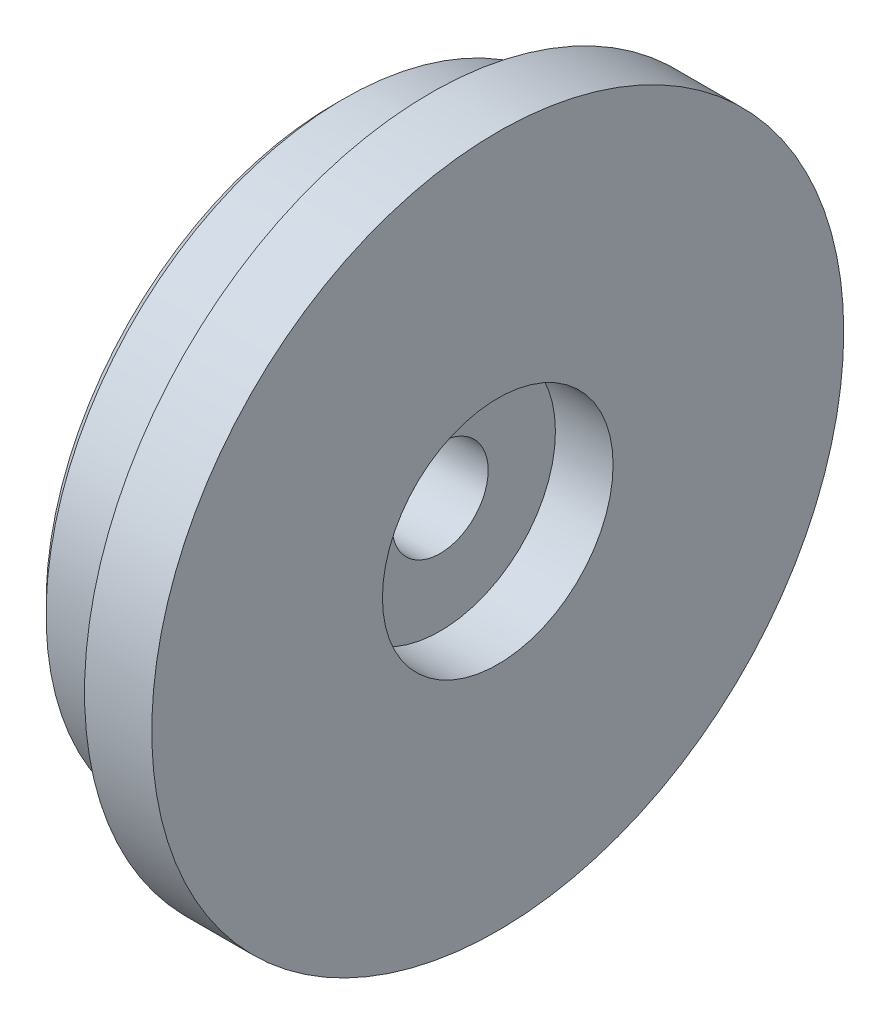
SolidWorks part; units mm, degrees
material "Alliage de zinc AC41A, brut"
ref_plane "Plan de face" through (0, 0, 0) normal (0, 0, 1) x (1, 0, 0)
ref_plane "Plan de dessus" through (0, 0, 0) normal (0, 1, 0) x (1, 0, 0)
ref_plane "Plan de droite" through (0, 0, 0) normal (1, 0, 0) x (0, 0, -1)
sketch "Esquisse1" plane through (0, 0, 0) normal (0, 0, 1) x (1, 0, 0)
  line L0 (0, 0) -> (0, 18) construction
  line L1 (0, 18) -> (-3.5, 18)
  line L2 (0, 18) -> (0, 6)
  line L3 (-3.5, 18) -> (-3.5, 15)
  line L4 (-3.5, 15) -> (-4.5, 15)
  line L5 (-4.5, 15) -> (-4.5, 15.5)
  line L6 (-4.5, 15.5) -> (-8, 15.5)
  line L8 (0, 6) -> (-3, 6)
  line L9 (-3, 6) -> (-3, 2.5)
  line L10 (-3, 2.5) -> (-8.5, 2.5)
  line L11 (-8, 15.5) -> (-8.5, 15)
  line L12 (-8.5, 2.5) -> (-8.5, 5)
  line L13 (-8.5, 5) -> (-5.75, 5)
  line L14 (-5, 5.75) -> (-5, 11.25)
  line L15 (-5.75, 12) -> (-8.5, 12)
  line L16 (-8.5, 12) -> (-8.5, 15)
  line L17 (-5, 11.25) -> (-5.75, 12)
  line L18 (-5.75, 5) -> (-5, 5.75)
  line L19 (0, 0) -> (-8.5, 0) construction
  point P8 (-8.5, 15.5)
  point P13 (-5, 5)
  point P15 (-5, 12)
  dimension "D1" = 18
  dimension "D2" = 3.5
  dimension "D3" = 12
  dimension "D4" = 3
  dimension "D5" = 1
  dimension "D6" = 0.5
  dimension "D8" = 2.5
  dimension "D9" = 3
  dimension "D10" = 3.5
  dimension "D11" = 5.5
  dimension "D12" = 3.5
  dimension "D14" = 7
  dimension "D15" = 3
  dimension "D16" = 3.5
revolve "Révolution1789" add sketch "Esquisse1" angle 360 about L19
cosmetic thread "Représentation de filetage1" parameters "D2"=30
cosmetic thread "Représentation de filetage2" parameters "D2"=6
